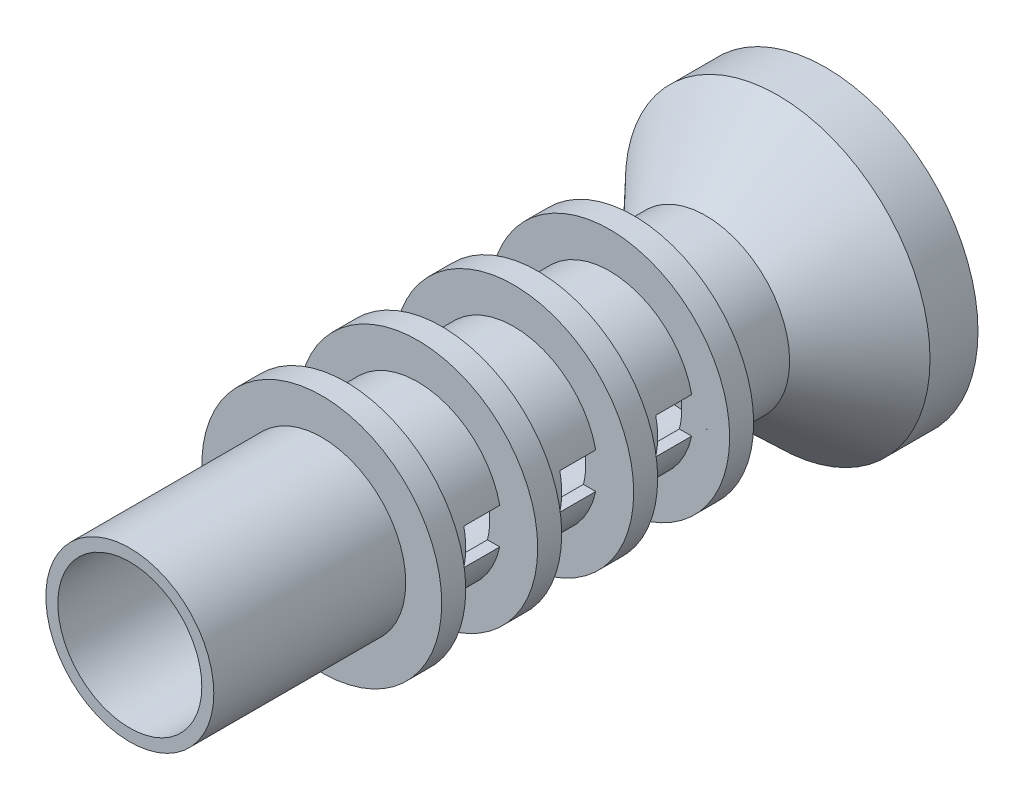
SolidWorks part; units mm, degrees
material "ABS"
ref_plane "正面" through (0, 0, 0) normal (0, 0, 1) x (1, 0, 0)
ref_plane "平面" through (0, 0, 0) normal (0, 1, 0) x (1, 0, 0)
ref_plane "右側面" through (0, 0, 0) normal (1, 0, 0) x (0, 0, -1)
sketch "ｽｹｯﾁ1" plane through (0, 0, 0) normal (0, 0, 1) x (1, 0, 0)
  circle A0 centre (0, 0) radius 3.5 construction
  circle A1 centre (0, 0) radius 6.35
  dimension "D1" = 7
  dimension "D2" = 12.7
ref_plane "平面1" through (0, 0, 5) normal (0, 0, 1) x (1, 0, 0)
sketch "ｽｹｯﾁ2" plane through (0, 0, 5) normal (0, 0, 1) x (1, 0, 0)
  circle A0 centre (0, 0) radius 3.5 construction
  circle A1 centre (0, 0) radius 3.5
ref_plane "平面2" through (0, 0, 29) normal (0, 0, 1) x (1, 0, 0)
ref_plane "平面3" through (0, 0, 24) normal (0, 0, 1) x (1, 0, 0)
sketch "ｽｹｯﾁ5" plane through (0, 0, 29) normal (0, 0, 1) x (1, 0, 0)
  circle A0 centre (0, 0) radius 6.35 construction
  circle A1 centre (0, 0) radius 6.35 construction
  circle A2 centre (0, 0) radius 3.5
  dimension "D1" = 7
extrude "ﾎﾞｽ - 押し出し3" add sketch "ｽｹｯﾁ2" along normal up to surface (19 mm away) contours A1 up to plane "平面3"
extrude "ﾎﾞｽ - 押し出し4" add sketch "ｽｹｯﾁ1" along normal blind 2 separate body
extrude "ﾎﾞｽ - 押し出し5" add sketch "ｽｹｯﾁ5" against normal blind 2
loft "ﾛﾌﾄ1" add section face at (6.35, 0, 2) section face at (3.5, 0, 5) connector at (-0.1759, 6.3476, 2) connector at (-0.0742, 3.4992, 5)
loft "ﾛﾌﾄ2" add section face at (3.5, 0, 24) section face at (3.5, 0, 27) connector at (-0.0749, 3.4992, 24) connector at (-0.0751, 3.4992, 27)
ref_plane "平面5" through (0, 0, 14.5) normal (0, 0, 1) x (1, 0, 0)
ref_plane "平面6" through (0, 0, 16) normal (0, 0, 1) x (1, 0, 0)
sketch "ｽｹｯﾁ9" plane through (0, 0, 16) normal (0, 0, 1) x (1, 0, 0)
  circle A0 centre (0, 0) radius 5
  dimension "D1" = 10
extrude "ﾎﾞｽ - 押し出し6" add sketch "ｽｹｯﾁ9" along normal blind 1
ref_plane "平面7" through (0, 0, 20) normal (0, 0, 1) x (1, 0, 0)
sketch "ｽｹｯﾁ10" plane through (0, 0, 20) normal (0, 0, 1) x (1, 0, 0)
  circle A1 centre (0, 0) radius 5
  circle A2 centre (0, 0) radius 5
  dimension "D1" = 0
extrude "ﾎﾞｽ - 押し出し7" add sketch "ｽｹｯﾁ10" along normal blind 1
mirror "ﾐﾗｰ3" about plane through (0, 0, 14.5) normal (0, 0, 1) of "ﾎﾞｽ - 押し出し7", "ﾎﾞｽ - 押し出し6"
sketch "ｽｹｯﾁ6" plane through (0, 0, 0) normal (0, 0, -1) x (-1, 0, 0)
  circle A0 centre (0, 0) radius 2.75
  dimension "D1" = 5.5
extrude "ｶｯﾄ - 押し出し1" cut sketch "ｽｹｯﾁ6" against normal blind 3
sketch "ｽｹｯﾁ7" plane through (0, 0, 3) normal (0, 0, -1) x (-1, 0, 0)
  circle A0 centre (0, 0) radius 1.8
  dimension "D1" = 3.6
extrude "ｶｯﾄ - 押し出し2" cut sketch "ｽｹｯﾁ7" against normal through all
sketch "ｽｹｯﾁ8" plane through (0, 0, 29) normal (0, 0, 1) x (1, 0, 0)
  circle A0 centre (0, 0) radius 3
  dimension "D1" = 6
extrude "ｶｯﾄ - 押し出し3" cut sketch "ｽｹｯﾁ8" against normal offset from surface (23 mm away) 3 up to face at (-1.8, 0, 3)
ref_plane "平面9" through (3.5, 0, 0) normal (1, 0, 0) x (0, 0, -1)
sketch "ｽｹｯﾁ11" plane through (3.5, 0, 0) normal (1, 0, 0) x (0, 0, -1)
  line L0 (0, 0) -> (-29, 0) construction
  line L1 (-29, 6.9851) -> (-29, -6.9851) construction
  line L2 (-17, 3.5) -> (-17, -3.5) construction
  line L3 (-18.5, 0.75) -> (-17, 0.75)
  line L4 (-18.5, 0.75) -> (-18.5, -0.75)
  line L5 (-18.5, -0.75) -> (-17, -0.75)
  line L6 (-17, 0.75) -> (-17, -0.75)
  line L7 (-18.5, 0.75) -> (-17, -0.75) construction
  line L8 (-18.5, -0.75) -> (-17, 0.75) construction
  line L9 (-13, 5) -> (-13, -5) construction
  line L10 (-14.5, 0.75) -> (-13, 0.75)
  line L11 (-14.5, 0.75) -> (-14.5, -0.75)
  line L12 (-14.5, -0.75) -> (-13, -0.75)
  line L13 (-13, 0.75) -> (-13, -0.75)
  line L14 (-14.5, 0.75) -> (-13, -0.75) construction
  line L15 (-14.5, -0.75) -> (-13, 0.75) construction
  line L16 (-9, 3.5) -> (-9, -3.5) construction
  line L17 (-10.5, 0.75) -> (-9, 0.75)
  line L18 (-10.5, 0.75) -> (-10.5, -0.75)
  line L19 (-10.5, -0.75) -> (-9, -0.75)
  line L20 (-9, 0.75) -> (-9, -0.75)
  line L21 (-10.5, 0.75) -> (-9, -0.75) construction
  line L22 (-10.5, -0.75) -> (-9, 0.75) construction
  point P5 (-17.75, 0)
  point P12 (-13.75, 0)
  point P19 (-9.75, 0)
  dimension "D1" = 1.5
  dimension "D2" = 1.5
extrude "ｶｯﾄ - 押し出し4" cut sketch "ｽｹｯﾁ11" against normal up to next
sketch "ｽｹｯﾁ12" plane through (0, 0, 0) normal (0, 0, -1) x (-1, 0, 0)
  line L0 (0, 0) -> (0, 2.75) construction
  line L1 (0, 0) -> (0.3745, 2.7244) construction
  line L2 (0, 0) -> (0.7419, 2.648) construction
  line L3 (0, 0) -> (1.0956, 2.5223) construction
  line L4 (0, 0) -> (1.4289, 2.3497) construction
  line L5 (0, 0) -> (1.7355, 2.1332) construction
  line L6 (0, 0) -> (2.0098, 1.877) construction
  line L7 (0, 0) -> (2.2467, 1.5859) construction
  line L8 (0, 0) -> (2.4417, 1.2652) construction
  line L9 (0, 0) -> (2.5912, 0.9209) construction
  line L10 (0, 0) -> (2.6925, 0.5595) construction
  line L11 (0, 0) -> (2.7436, 0.1877) construction
  line L12 (0, 0) -> (2.7436, -0.1877) construction
  line L13 (0, 0) -> (2.6925, -0.5595) construction
  line L14 (0, 0) -> (2.5912, -0.9209) construction
  line L15 (0, 0) -> (2.4417, -1.2652) construction
  line L16 (0, 0) -> (2.2467, -1.5859) construction
  line L17 (0, 0) -> (2.0098, -1.877) construction
  line L18 (0, 0) -> (1.7355, -2.1332) construction
  line L19 (0, 0) -> (1.4289, -2.3497) construction
  line L20 (0, 0) -> (1.0956, -2.5223) construction
  line L21 (0, 0) -> (0.7419, -2.648) construction
  line L22 (0, 0) -> (0.3745, -2.7244) construction
  line L23 (0, 0) -> (0, -2.75) construction
  line L24 (0, 0) -> (-0.3745, -2.7244) construction
  line L25 (0, 0) -> (-0.7419, -2.648) construction
  line L26 (0, 0) -> (-1.0956, -2.5223) construction
  line L27 (0, 0) -> (-1.4289, -2.3497) construction
  line L28 (0, 0) -> (-1.7355, -2.1332) construction
  line L29 (0, 0) -> (-2.0098, -1.877) construction
  line L30 (0, 0) -> (-2.2467, -1.5859) construction
  line L31 (0, 0) -> (-2.4417, -1.2652) construction
  line L32 (0, 0) -> (-2.5912, -0.9209) construction
  line L33 (0, 0) -> (-2.6925, -0.5595) construction
  line L34 (0, 0) -> (-2.7436, -0.1877) construction
  line L35 (0, 0) -> (-2.7436, 0.1877) construction
  line L36 (0, 0) -> (-2.6925, 0.5595) construction
  line L37 (0, 0) -> (-2.5912, 0.9209) construction
  line L38 (0, 0) -> (-2.4417, 1.2652) construction
  line L39 (0, 0) -> (-2.2467, 1.5859) construction
  line L40 (0, 0) -> (-2.0098, 1.877) construction
  line L41 (0, 0) -> (-1.7355, 2.1332) construction
  line L42 (0, 0) -> (-1.4289, 2.3497) construction
  line L43 (0, 0) -> (-1.0956, 2.5223) construction
  line L44 (0, 0) -> (-0.7419, 2.648) construction
  line L45 (0, 0) -> (-0.3745, 2.7244) construction
  line L46 (0, 0) -> (0.2081, 3.0429) construction
  line L47 (0.2081, 3.0429) -> (-0.0626, 2.7493)
  line L48 (-0.0626, 2.7493) -> (0, 0) construction
  line L49 (0, 0) -> (0.4364, 2.7152) construction
  line L50 (0.4364, 2.7152) -> (0.2081, 3.0429)
  line L51 (1.0214, 2.8739) -> (0.6815, 2.6642)
  line L52 (1.1527, 2.4967) -> (1.0214, 2.8739)
  line L53 (1.7589, 2.4918) -> (1.375, 2.3816)
  line L54 (1.7836, 2.0931) -> (1.7589, 2.4918)
  line L55 (2.3659, 1.9248) -> (1.9666, 1.9223)
  line L56 (2.2822, 1.5343) -> (2.3659, 1.9248)
  line L57 (2.7975, 1.2151) -> (2.4123, 1.3204)
  line L58 (2.6115, 0.8617) -> (2.7975, 1.2151)
  line L59 (3.0216, 0.4153) -> (2.679, 0.6206)
  line L60 (2.7472, 0.1252) -> (3.0216, 0.4153)
  line L61 (3.0216, -0.4153) -> (2.7472, -0.1252)
  line L62 (2.679, -0.6206) -> (3.0216, -0.4153)
  line L63 (2.7975, -1.2151) -> (2.6115, -0.8617)
  line L64 (2.4123, -1.3204) -> (2.7975, -1.2151)
  line L65 (2.3659, -1.9248) -> (2.2822, -1.5343)
  line L66 (1.9666, -1.9223) -> (2.3659, -1.9248)
  line L67 (1.7589, -2.4918) -> (1.7836, -2.0931)
  line L68 (1.375, -2.3816) -> (1.7589, -2.4918)
  line L69 (1.0214, -2.8739) -> (1.1527, -2.4967)
  line L70 (0.6815, -2.6642) -> (1.0214, -2.8739)
  line L71 (0.2081, -3.0429) -> (0.4364, -2.7152)
  line L72 (-0.0626, -2.7493) -> (0.2081, -3.0429)
  line L73 (-0.6205, -2.9862) -> (-0.3123, -2.7322)
  line L74 (-0.802, -2.6304) -> (-0.6205, -2.9862)
  line L75 (-1.4032, -2.708) -> (-1.0379, -2.5466)
  line L76 (-1.482, -2.3165) -> (-1.4032, -2.708)
  line L77 (-2.0818, -2.229) -> (-1.6865, -2.1722)
  line L78 (-2.052, -1.8308) -> (-2.0818, -2.229)
  line L79 (-2.606, -1.5847) -> (-2.21, -1.6366)
  line L80 (-2.4699, -1.2093) -> (-2.606, -1.5847)
  line L81 (-2.9369, -0.8229) -> (-2.5696, -0.9797)
  line L82 (-2.7045, -0.4981) -> (-2.9369, -0.8229)
  line L83 (-3.05, 0) -> (-2.7386, -0.2501)
  line L84 (-2.7386, 0.2501) -> (-3.05, 0)
  line L85 (-2.9369, 0.8229) -> (-2.7045, 0.4981)
  line L86 (-2.5696, 0.9797) -> (-2.9369, 0.8229)
  line L87 (-2.606, 1.5847) -> (-2.4699, 1.2093)
  line L88 (-2.21, 1.6366) -> (-2.606, 1.5847)
  line L89 (-2.0818, 2.229) -> (-2.052, 1.8308)
  line L90 (-1.6865, 2.1722) -> (-2.0818, 2.229)
  line L91 (-1.4032, 2.708) -> (-1.482, 2.3165)
  line L92 (-1.0379, 2.5466) -> (-1.4032, 2.708)
  line L93 (-0.6205, 2.9862) -> (-0.802, 2.6304)
  line L94 (-0.3123, 2.7322) -> (-0.6205, 2.9862)
  circle A0 centre (0, 0) radius 2.75 construction
  circle A1 centre (0, 0) radius 3.05 construction
  arc A2 (0, 2.75) -> (0.3745, 2.7244) centre (0, 0) cw construction
  circle A3 centre (0, 0) radius 2.75 construction
  arc A4 (-0.0626, 2.7493) -> (0.4364, 2.7152) centre (0, 0) cw
  arc A5 (0.6815, 2.6642) -> (1.1527, 2.4967) centre (0, 0) cw
  arc A6 (1.375, 2.3816) -> (1.7836, 2.0931) centre (0, 0) cw
  arc A7 (1.9666, 1.9223) -> (2.2822, 1.5343) centre (0, 0) cw
  arc A8 (2.4123, 1.3204) -> (2.6115, 0.8617) centre (0, 0) cw
  arc A9 (2.679, 0.6206) -> (2.7472, 0.1252) centre (0, 0) cw
  arc A10 (2.7472, -0.1252) -> (2.679, -0.6206) centre (0, 0) cw
  arc A11 (2.6115, -0.8617) -> (2.4123, -1.3204) centre (0, 0) cw
  arc A12 (2.2822, -1.5343) -> (1.9666, -1.9223) centre (0, 0) cw
  arc A13 (1.7836, -2.0931) -> (1.375, -2.3816) centre (0, 0) cw
  arc A14 (1.1527, -2.4967) -> (0.6815, -2.6642) centre (0, 0) cw
  arc A15 (0.4364, -2.7152) -> (-0.0626, -2.7493) centre (0, 0) cw
  arc A16 (-0.3123, -2.7322) -> (-0.802, -2.6304) centre (0, 0) cw
  arc A17 (-1.0379, -2.5466) -> (-1.482, -2.3165) centre (0, 0) cw
  arc A18 (-1.6865, -2.1722) -> (-2.052, -1.8308) centre (0, 0) cw
  arc A19 (-2.21, -1.6366) -> (-2.4699, -1.2093) centre (0, 0) cw
  arc A20 (-2.5696, -0.9797) -> (-2.7045, -0.4981) centre (0, 0) cw
  arc A21 (-2.7386, -0.2501) -> (-2.7386, 0.2501) centre (0, 0) cw
  arc A22 (-2.7045, 0.4981) -> (-2.5696, 0.9797) centre (0, 0) cw
  arc A23 (-2.4699, 1.2093) -> (-2.21, 1.6366) centre (0, 0) cw
  arc A24 (-2.052, 1.8308) -> (-1.6865, 2.1722) centre (0, 0) cw
  arc A25 (-1.482, 2.3165) -> (-1.0379, 2.5466) centre (0, 0) cw
  arc A26 (-0.802, 2.6304) -> (-0.3123, 2.7322) centre (0, 0) cw
  point P53 (0, 0)
  point P54 (0.1877, 2.7436)
  point P56 (0.1877, 2.7436)
  point P129 (0, 0)
  dimension "D2" = 6.1
  dimension "D3" = 10.435
  dimension "D1" = 46
  dimension "D4" = 23
extrude "ｶｯﾄ - 押し出し5" cut sketch "ｽｹｯﾁ12" against normal up to surface (3 mm away) up to face at (-1.8, 0, 3)
equation "\"D3@ｽｹｯﾁ12\"=360/23*2/3"
